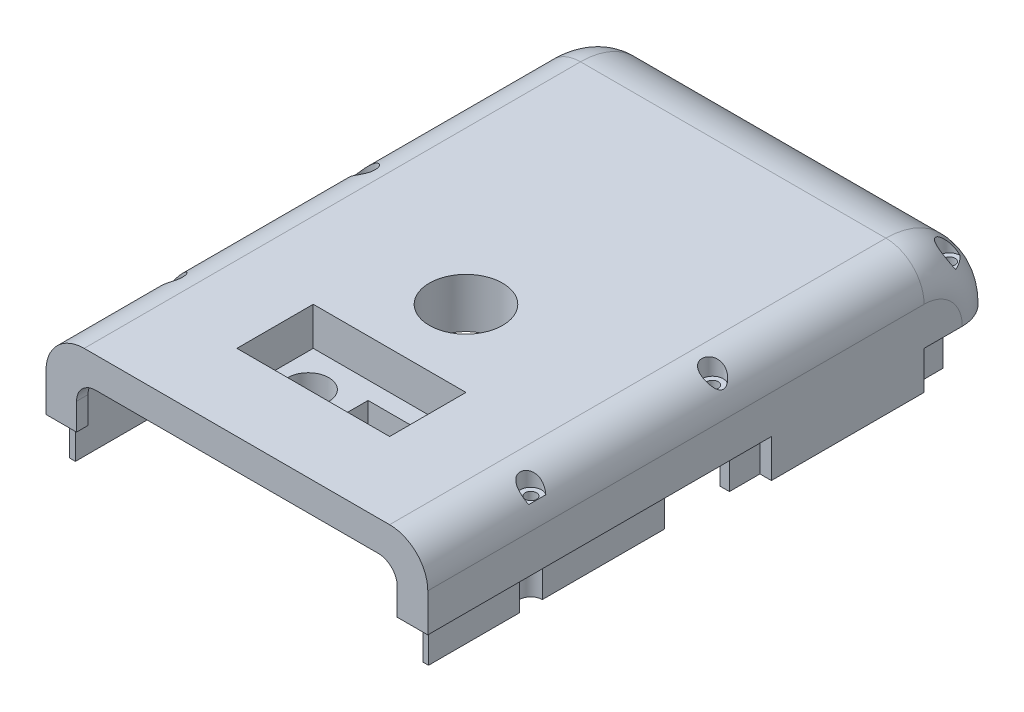
SolidWorks part; units mm, degrees
other "标注1"
sketch "草图22" plane through (50, -10, -75) normal (0.0366, -0.9706, -0.2378) x (0.174, -0.2282, 0.9579)
material "硅橡胶"
ref_plane "Front" through (0, 0, 0) normal (0, 0, 1) x (1, 0, 0)
ref_plane "Top" through (0, 0, 0) normal (0, 1, 0) x (1, 0, 0)
ref_plane "Right" through (0, 0, 0) normal (1, 0, 0) x (0, 0, -1)
sketch "草图1" plane through (0, 0, 0) normal (0, 1, 0) x (1, 0, 0)
  line L5 (50, 75) -> (-50, 75)
  line L6 (50, 75) -> (50, -75)
  line L7 (50, -75) -> (-50, -75)
  line L8 (-50, 75) -> (-50, -75)
  line L9 (50, 75) -> (-50, -75) construction
  line L10 (50, -75) -> (-50, 75) construction
  point P0 (0, 0)
  dimension "D1" = 100
  dimension "D2" = 150
extrude "凸台-拉伸1" add sketch "草图1" along normal blind 20
fillet "圆角1" radius 10 4 edges at (-50, 10, -75) (50, 10, -75) (50, 20, 0) (-50, 20, 0)
sketch "草图4" plane through (0, 20, 0) normal (0, 1, 0) x (1, 0, 0)
  line L0 (0, 0) -> (0, -50.1106) construction
  line L1 (-40, -75) -> (40, -75) construction
  line L2 (-20, -35) -> (20, -35)
  line L3 (-20, -35) -> (-20, -55)
  line L4 (-20, -55) -> (20, -55)
  line L5 (20, -35) -> (20, -55)
  point P6 (0, -35)
  dimension "D1" = 40
  dimension "D2" = 20
  dimension "D3" = 20
fillet "圆角2" radius 20 3 edges at (-47.0711, 17.0711, -72.0711) (47.0711, 17.0711, -72.0711) (0, 20, -75)
extrude "切除-拉伸4" cut sketch "草图4" against normal blind 10
shell "抽壳6" thickness 3 removed face at (0, 0, -22.357)
sketch "草图5" plane through (0, 0, 0) normal (0, -1, 0) x (1, 0, 0)
  line L0 (47, 72) -> (47, -65) construction
  line L1 (50, -55) -> (47, -55)
  line L2 (50, -55) -> (50, -15)
  line L3 (50, -15) -> (47, -15)
  line L4 (47, -55) -> (47, -15)
  line L5 (-47, -65) -> (-47, 72) construction
  line L6 (-50, -55) -> (-47, -55)
  line L7 (-50, -55) -> (-50, -15)
  line L8 (-50, -15) -> (-47, -15)
  line L9 (-47, -55) -> (-47, -15)
  line L10 (-50, -15) -> (-47, -15) construction
  dimension "D1" = 40
extrude "凸台-拉伸2" add sketch "草图5" along normal blind 10
sketch "草图6" plane through (0, 0, 0) normal (0, -1, 0) x (1, 0, 0)
  line L0 (47, 72) -> (47, -15) construction
  line L1 (44.5, -63) -> (47, -63)
  line L2 (44.5, -63) -> (44.5, -7)
  line L3 (44.5, -7) -> (47, -7)
  line L4 (47, -63) -> (47, -7)
  line L5 (44.3, -7) -> (47, -7) construction
  line L6 (-47, -65) -> (-47, -55) construction
  line L7 (-44.5, -7) -> (-47, -7)
  line L8 (-44.5, -7) -> (-44.5, -63)
  line L9 (-44.5, -63) -> (-47, -63)
  line L10 (-47, -7) -> (-47, -63)
  line L11 (-44.3, -63) -> (-47, -63) construction
  dimension "D1" = 2.5
  dimension "D2" = 2.5
extrude "凸台-拉伸3" add sketch "草图6" along normal blind 10 and the other way up to next
sketch "草图7" plane through (0, 0, 0) normal (0, -1, 0) x (1, 0, 0)
  line L0 (-47, 71.8) -> (-47, 48)
  line L1 (-47, -7) -> (-47, 72) construction
  line L2 (-47, 42) -> (-47, 10)
  line L3 (-47, 10) -> (-50, 10) construction
  line L4 (-45.5, 71.8) -> (-45.5, 49.2426)
  line L5 (-45.5, 40.7574) -> (-45.5, 10)
  line L6 (-47, 10) -> (-45.5, 10)
  line L8 (0, 0) -> (0, 56.9208) construction
  line L9 (47, 71.8) -> (45.5, 71.8)
  line L10 (47, 10) -> (45.5, 10)
  line L11 (45.5, 40.7574) -> (45.5, 10)
  line L12 (45.5, 71.8) -> (45.5, 49.2426)
  line L13 (47, 42) -> (47, 10)
  line L14 (47, 71.8) -> (47, 48)
  line L15 (-37.8, -72) -> (37.3, -72)
  line L16 (38.3, -72) -> (-38.3, -72) construction
  line L17 (40, -72) -> (-40, -72) construction
  line L21 (-37.8, -71.0662) -> (37.3, -71.0662)
  line L25 (-37.8, -71.0662) -> (-37.8, -72)
  line L26 (37.3, -72) -> (37.3, -71.0662)
  line L28 (46.1809, -63.059) -> (46.005, -63.1577) construction
  line L29 (45.2278, -63.6754) -> (45.2278, -63.6754) construction
  line L30 (-46.3438, -62.3347) -> (-45.8341, -63.0037) construction
  line L31 (-45.4607, -63.8596) -> (-45.4607, -63.8596) construction
  line L32 (-47, 72) -> (-47, 48) construction
  line L33 (-47, 71.8) -> (-45.5, 71.8)
  line L35 (-47, 72) -> (47, 72) construction
  line L36 (-45.5, 72) -> (-45.5, 49.2426) construction
  arc A0 (-47, 42) -> (-47, 48) centre (-47, 45) ccw construction
  arc A1 (-47, 42) -> (-47, 48) centre (-47, 45) ccw
  arc A2 (-45.5, 40.7574) -> (-45.5, 49.2426) centre (-47, 45) ccw
  arc A3 (45.5, 40.7574) -> (45.5, 49.2426) centre (47, 45) cw
  arc A4 (47, 42) -> (47, 48) centre (47, 45) cw
  arc A9 (37.3, -72) -> (46.1809, -63.059) centre (37.3, -63.1189) ccw construction
  arc A10 (37.3, -71.0662) -> (45.2278, -63.6754) centre (37.3, -63.1189) ccw construction
  arc A11 (-45.4607, -63.8596) -> (-37.8, -71.0662) centre (-37.8, -63.3911) ccw construction
  arc A12 (-46.3438, -62.3347) -> (-37.8, -72) centre (-37.8, -63.3911) ccw construction
  arc A13 (37.8, -72) -> (40.8, -69) centre (37.8, -69) ccw construction
  dimension "D3" = 0.5
  dimension "D2" = 0.5
  dimension "D4" = 0.2
  dimension "D5" = 0.2
  dimension "D1" = 1.5
extrude "凸台-拉伸4" add sketch "草图7" along normal blind 10 and the other way up to next
sketch "草图9" plane through (0, 0, 0) normal (0, -1, 0) x (-1, 0, 0)
  line L0 (-47, -48) -> (-47, -42) construction
  line L1 (47, -42) -> (47, -48) construction
  line L4 (-47, -10) -> (-47, 7) construction
  line L5 (-47, -3) -> (-47, 7)
  line L6 (-42.8, 15) -> (-44.5, 15)
  line L7 (-44.5, 7) -> (-44.5, 63) construction
  line L8 (-44.5, 15) -> (-44.5, 7)
  line L9 (-44.5, 7) -> (-47, 7)
  line L11 (-40.8, 13) -> (-40.8, 1)
  line L12 (-42.8, -1) -> (-45, -1)
  line L13 (-45, -1) -> (-43.3, -1) construction
  line L14 (0, 0) -> (0, 18.6927)
  line L15 (42.8, -1) -> (45, -1)
  line L16 (40.8, 13) -> (40.8, 1)
  line L17 (44.5, 7) -> (47, 7)
  line L18 (44.5, 15) -> (44.5, 7)
  line L19 (42.8, 15) -> (44.5, 15)
  line L20 (47, -3) -> (47, 7)
  circle A0 centre (-47, -45) radius 3
  circle A1 centre (47, -45) radius 3
  arc A2 (-45, -1) -> (-47, -3) centre (-45, -3) ccw
  arc A3 (-40.8, 1) -> (-42.8, -1) centre (-42.8, 1) cw
  arc A4 (40.8, 1) -> (42.8, -1) centre (42.8, 1) ccw
  arc A5 (45, -1) -> (47, -3) centre (45, -3) cw
  arc A6 (-42.8, 15) -> (-40.8, 13) centre (-42.8, 13) cw
  arc A7 (42.8, 15) -> (40.8, 13) centre (42.8, 13) ccw
  point P46 (-40.8, 15)
  point P49 (40.8, 15)
  line M4 (47, 7) -> (47, -10)
  line M6 (47, -42) -> (47, -48)
  line M12 (-47, -48) -> (-47, -42)
  line M14 (-47, -10) -> (-47, 7)
  dimension "D1" = 2
  dimension "D2" = 2
  dimension "D3" = 2
extrude "凸台-拉伸5" add sketch "草图9" against normal up to body separate body contours L15 A5 L17 L18 L19 L16 A4 M4 | A3 L11 L6 L8 L9 A2 L12 M14 | A0 M12 | A1 M6 region at (43.5149, 0, -5.8863) region at (-43.5149, 0, -5.8863) region at (45.7268, 0, 45) region at (-45.7268, 0, 45)
sketch "草图10" plane through (0, 0, 0) normal (0, -1, 0) x (1, 0, 0)
  line L3 (-40, -72) -> (-40, -57)
  line L4 (-42, -55) -> (-44.5, -55)
  line L7 (-44.5, -55) -> (-44.5, -63)
  line L10 (-44.5, -63) -> (-47, -63)
  line L11 (-47, -63) -> (-47, -65)
  line L12 (0, 0) -> (0, -94.4608) construction
  line L13 (47, -63) -> (47, -65)
  line L14 (44.5, -63) -> (47, -63)
  line L15 (44.5, -55) -> (44.5, -63)
  line L16 (42, -55) -> (44.5, -55)
  line L17 (40, -72) -> (40, -57)
  arc A2 (-40, -57) -> (-42, -55) centre (-42, -57) ccw
  arc A4 (-47, -65) -> (-40, -72) centre (-40, -65) ccw
  arc A5 (47, -65) -> (40, -72) centre (40, -65) cw
  arc A6 (40, -57) -> (42, -55) centre (42, -57) cw
  point P27 (-40, -55)
  point P36 (40, -55)
  dimension "D1" = 2
extrude "凸台-拉伸6" add sketch "草图10" against normal up to body separate body
sketch "草图11" plane through (0, 0, 0) normal (0, -1, 0) x (1, 0, 0)
  circle A0 centre (-45.65, -66) radius 1.5
  circle A1 centre (-45.6051, -4) radius 1.5
  circle A2 centre (-47, 45) radius 1.4854
  circle A3 centre (47, 45) radius 1.5
  circle A4 centre (45.6051, -4) radius 1.5
  circle A5 centre (45.65, -66) radius 1.5
extrude "切除-拉伸1" cut sketch "草图11" against normal through all
sketch "草图13" plane through (0, 0, 75) normal (0, 0, 1) x (1, 0, 0)
  line L0 (-50, 0) -> (50, 0) construction
  line L5 (-42, 0) -> (42, 0)
  line L6 (-42, 0) -> (-42, 7)
  line L7 (-37, 12) -> (37, 12)
  line L16 (42, 0) -> (42, 7)
  line L17 (-20, 20) -> (20, 20) construction
  line L18 (50, 10) -> (50, 0) construction
  line L19 (-50, 10) -> (-50, 0) construction
  arc A4 (42, 7) -> (37, 12) centre (37, 7) ccw
  arc A5 (-37, 12) -> (-42, 7) centre (-37, 7) ccw
  dimension "D1" = 8
  dimension "D4" = 5
  dimension "D2" = 8
  dimension "D3" = 8
extrude "切除-拉伸3" cut sketch "草图13" against normal blind 10
sketch "草图14" plane through (0, 10, 0) normal (0, 1, 0) x (1, 0, 0)
  line L0 (-20, -45) -> (69.8907, -45) construction
  line L1 (-20, -35) -> (-20, -55) construction
  circle A0 centre (-11.3127, -45) radius 5.4
  dimension "D1" = 10.8
extrude "切除-拉伸5" cut sketch "草图14" against normal through all
sketch "草图15" plane through (0, 7, 0) normal (0, -1, 0) x (1, 0, 0)
  line L0 (-14.3127, 52.846) -> (-14.3127, 58)
  line L1 (-23, 58) -> (23, 58) construction
  line L2 (-14.3127, 58) -> (-8.3127, 58)
  line L3 (-23, 58) -> (23, 58) construction
  line L4 (-8.3127, 58) -> (-8.3127, 52.846)
  line L5 (-11.3127, 45) -> (-11.3127, 65.9273) construction
  circle A0 centre (-11.3127, 45) radius 5.4
  arc A1 (-14.3127, 52.846) -> (-8.3127, 52.846) centre (-11.3127, 45) ccw
  circle A2 centre (-11.3127, 45) radius 5.4 construction
  circle A3 centre (-11.3127, 45) radius 8.4 construction
  point P9 (-3.4351, 47.4084)
  dimension "D2" = 6
  dimension "D1" = 3
extrude "凸台-拉伸7" add sketch "草图15" along normal blind 10
sketch "草图16" plane through (0, 0, 58) normal (0, 0, 1) x (1, 0, 0)
  line L0 (-8.3127, -3) -> (-8.3127, 7) construction
  line L1 (-8.3127, -3) -> (-14.3127, -3) construction
  circle A0 centre (-11.3127, 2) radius 1.4862
  dimension "D1" = 3
  dimension "D2" = 5
extrude "切除-拉伸6" cut sketch "草图16" against normal up to next
sketch "草图17" plane through (0, 10, 0) normal (0, 1, 0) x (1, 0, 0)
  line L0 (20, -55) -> (20, -35) construction
  line L1 (-1, -39.639) -> (17, -39.639)
  line L2 (-1, -39.639) -> (-1, -49.639)
  line L3 (-1, -49.639) -> (17, -49.639)
  line L4 (17, -39.639) -> (17, -49.639)
  dimension "D1" = 10
  dimension "D2" = 18
  dimension "D3" = 3
extrude "切除-拉伸7" cut sketch "草图17" against normal up to next
sketch "草图18" plane through (0, 7, 0) normal (0, -1, 0) x (1, 0, 0)
  line L0 (17, 39.639) -> (17, 49.639) construction
  line L1 (-1, 49.639) -> (17, 49.639)
  line L2 (-1, 49.639) -> (-1, 39.639)
  line L3 (-1, 39.639) -> (17, 39.639)
  line L4 (17, 49.639) -> (17, 39.639)
  line L5 (-4, 52.639) -> (-4, 36.639)
  line L6 (-4, 36.639) -> (20, 36.639)
  line L7 (20, 52.639) -> (20, 36.639)
  line L8 (-4, 52.639) -> (5, 52.639)
  line L9 (5, 52.639) -> (5, 58)
  line L10 (-8.3127, 58) -> (23, 58) construction
  line L11 (5, 58) -> (11, 58)
  line L12 (-23, 58) -> (23, 58) construction
  line L13 (11, 58) -> (11, 52.639)
  line L14 (8, 52.639) -> (8, 62.2572) construction
  line L15 (11, 52.639) -> (20, 52.639)
  line L17 (-4, 52.639) -> (20, 52.639) construction
  dimension "D2" = 6
  dimension "D1" = 3
extrude "凸台-拉伸8" add sketch "草图18" along normal blind 10
sketch "草图19" plane through (0, 0, 58) normal (0, 0, 1) x (1, 0, 0)
  line L0 (11, -3) -> (11, 7) construction
  line L1 (11, -3) -> (5, -3) construction
  circle A0 centre (8, 2) radius 1.5
  dimension "D3" = 3
  dimension "D1" = 3
  dimension "D2" = 5
extrude "切除-拉伸8" cut sketch "草图19" against normal up to next
fillet "圆角3" radius 1 24 edges at (5, -3, 55.3195) (-4, 7, 50.8862) (11, -3, 55.3195) (-4, 7, 38.7528) (5, 2, 52.639) (0.5, -3, 52.639) (-4, 2, 52.639) (0.5, 7, 52.639) (20, 2, 52.639) (15.5, -3, 52.639) (11, 2, 52.639) (15.5, 7, 52.639) (-4, 2, 36.639) (8, -3, 36.639) (20, 2, 36.639) (8, 7, 36.639) (20, 7, 44.639) (-14.3127, -3, 55.423) (-4, -3, 38.7528) (-17.6787, 7, 39.5197) (-14.3127, 2, 52.846) (-17.6787, -3, 39.5197) (-4, 2, 40.8666) (-8.3127, -3, 55.423)
sketch "草图20" plane through (0, 20, 0) normal (0, 1, 0) x (1, 0, 0)
  line L0 (20, -35) -> (-20, -35) construction
  circle A0 centre (0, -15) radius 9.6
  dimension "D1" = 19.2
  dimension "D2" = 20
extrude "切除-拉伸9" cut sketch "草图20" against normal up to next
sketch "草图21" plane through (0, 17, 0) normal (0, -1, 0) x (-1, 0, 0)
  circle A0 centre (0, -15) radius 9.6
  circle A1 centre (0, -15) radius 12.6
  circle A2 centre (0, -15) radius 9.6 construction
  dimension "D1" = 3
extrude "凸台-拉伸9" add sketch "草图21" along normal blind 10
sketch "草图27" plane through (0, 20, 0) normal (0, 1, 0) x (1, 0, 0)
  circle A2 centre (45.6051, 4) radius 2.8
  circle A3 centre (47, -45) radius 2.8
  circle A4 centre (-47, -45) radius 2.8
  circle A5 centre (-45.6051, 4) radius 2.8
extrude "切除-拉伸12" cut sketch "草图27" against normal blind 5
sketch "草图28" plane through (0, 20, 0) normal (0, 1, 0) x (1, 0, 0)
  circle A0 centre (-45.65, 66) radius 2.8
  circle A1 centre (45.65, 66) radius 2.8
  dimension "D1" = 5.6
extrude "切除-拉伸13" cut sketch "草图28" against normal blind 8
